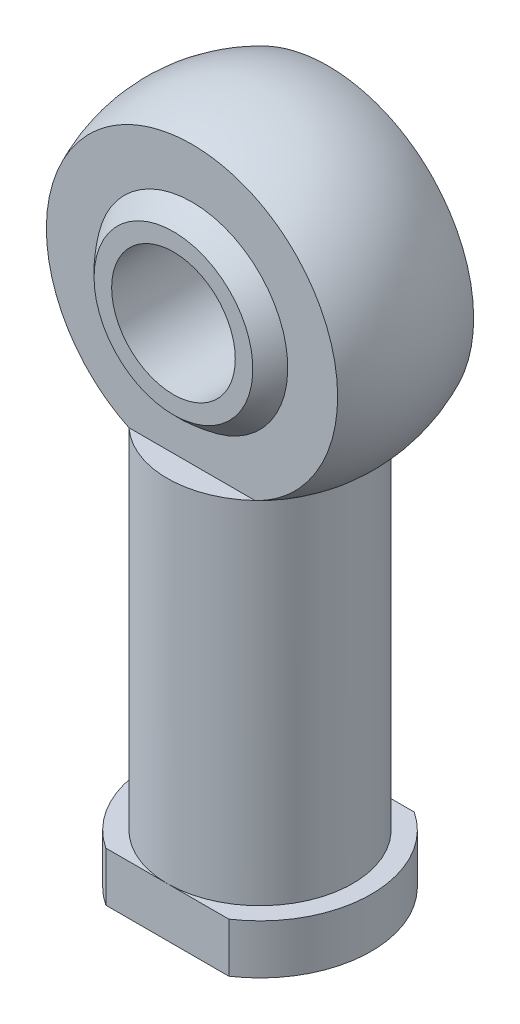
SolidWorks part; units mm, degrees
ref_plane "Front Plane" through (0, 0, 0) normal (0, 0, 1) x (1, 0, 0)
ref_plane "Top Plane" through (0, 0, 0) normal (0, 1, 0) x (1, 0, 0)
ref_plane "Right Plane" through (0, 0, 0) normal (1, 0, 0) x (0, 0, -1)
sketch "Sketch1" plane through (0, 0, 0) normal (0, 0, 1) x (1, 0, 0)
  line L0 (0, 0) -> (0, 43) construction
  line L1 (-7.5, 4) -> (-7.5, 32.3816)
  line L2 (-7.5, 4) -> (-9, 4)
  line L3 (-9, 4) -> (-9, 0)
  line L4 (-9, 0) -> (0, 0)
  line L5 (0, 0) -> (0, 56)
  circle A0 centre (0, 43) radius 9.5
  circle A1 centre (0, 43) radius 10.5
  circle A2 centre (0, 43) radius 13
  dimension "D2" = 26
  dimension "D3" = 21
  dimension "D4" = 19
  dimension "D1" = 43
  dimension "D5" = 15
  dimension "D6" = 18
  dimension "D7" = 4
revolve "Revolve5" add sketch "Sketch1" angle 360 about L0 region at (-0.2348, 53, 0)
revolve "Revolve6" add sketch "Sketch1<7>" angle 360 about L0 region at (-3.9102, 15.0497, 0) region at (-12.1132, 46.8466, 0)
sketch "Sketch1<7>" plane through (0, 0, 0) normal (0, 0, 1) x (1, 0, 0) same geometry as "Sketch1"
sketch "Sketch3" plane through (0, 0, 0) normal (1, 0, 0) x (0, 0, -1)
  line L0 (0, 0) -> (0, 56) construction
  line L1 (-23.0793, 62.8909) -> (-5.5, 62.8909)
  line L2 (-23.0793, 62.8909) -> (-23.0793, 32.3816)
  line L3 (-23.0793, 32.3816) -> (-5.5, 32.3816)
  line L4 (-5.5, 62.8909) -> (-5.5, 32.3816)
  line L5 (0, 0) -> (0, 56) construction
  line L6 (7.5, 32.3816) -> (-7.5, 32.3816) construction
  line L7 (23.0793, 32.3816) -> (5.5, 32.3816)
  line L8 (5.5, 62.8909) -> (5.5, 32.3816)
  line L9 (23.0793, 62.8909) -> (5.5, 62.8909)
  line L10 (23.0793, 62.8909) -> (23.0793, 32.3816)
  dimension "D1" = 11
extrude "Cut-Extrude3" cut sketch "Sketch3" against normal through all both and the other way through all
revolve "Revolve7" add sketch "Sketch1<8>" angle 360 about L0 region at (-4.0319, 43, 0)
sketch "Sketch1<8>" plane through (0, 0, 0) normal (0, 0, 1) x (1, 0, 0) same geometry as "Sketch1"
sketch "Sketch4" plane through (0, 0, 0) normal (1, 0, 0) x (0, 0, -1)
  line L0 (0, 56) -> (0, 30) construction
  line L1 (-21.9327, 55.3399) -> (-7, 55.3399)
  line L2 (-21.9327, 55.3399) -> (-21.9327, 35.4641)
  line L3 (-21.9327, 35.4641) -> (-7, 35.4641)
  line L4 (-7, 55.3399) -> (-7, 35.4641)
  line L5 (0, 56) -> (0, 30) construction
  line L6 (21.9327, 35.4641) -> (7, 35.4641)
  line L7 (7, 55.3399) -> (7, 35.4641)
  line L8 (21.9327, 55.3399) -> (7, 55.3399)
  line L9 (21.9327, 55.3399) -> (21.9327, 35.4641)
  dimension "D1" = 14
extrude "Cut-Extrude4" cut sketch "Sketch4" against normal through all both and the other way through all
sketch "Sketch5" plane through (0, 0, 7) normal (0, 0, 1) x (1, 0, 0)
  circle A0 centre (0, 43) radius 5
  dimension "D1" = 10
extrude "Cut-Extrude5" cut sketch "Sketch5" against normal through all both and the other way through all
sketch "Sketch6" plane through (0, 0, 0) normal (0, 1, 0) x (1, 0, 0)
  line L0 (-15.9573, 0) -> (23.5227, 0) construction
  line L1 (-7.5611, 12.7928) -> (8.4336, 12.7928)
  line L2 (-7.5611, 12.7928) -> (-7.5611, 7.5)
  line L3 (-7.5611, 7.5) -> (8.4336, 7.5)
  line L4 (8.4336, 12.7928) -> (8.4336, 7.5)
  line L5 (-7.5611, -7.5) -> (8.4336, -7.5)
  line L6 (8.4336, -12.7928) -> (8.4336, -7.5)
  line L7 (-7.5611, -12.7928) -> (8.4336, -12.7928)
  line L8 (-7.5611, -12.7928) -> (-7.5611, -7.5)
  circle A0 centre (0, 0) radius 7.5 construction
extrude "Cut-Extrude6" cut sketch "Sketch6" along normal through all both and the other way through all
sketch "Sketch7" plane through (0, 0, 0) normal (0, -1, 0) x (1, 0, 0)
  circle A0 centre (0, 0) radius 5
  dimension "D1" = 10
extrude "Cut-Extrude7" cut sketch "Sketch7" against normal blind 25 and the other way through all
